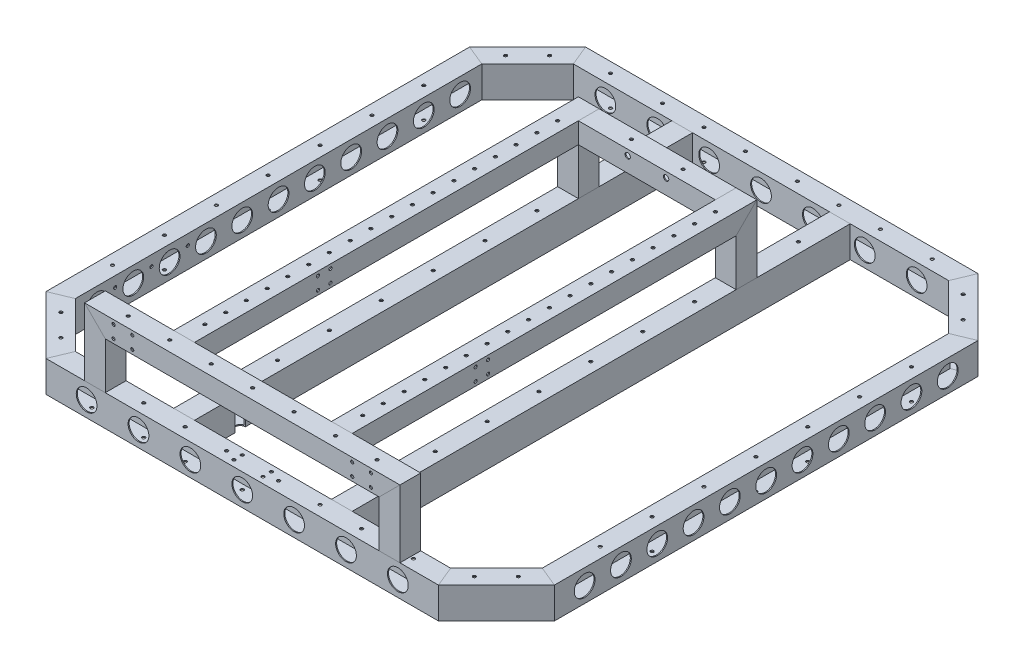
SolidWorks part; units mm, degrees
material "7050-T73510"
ref_plane "前视基准面" through (0, 0, 0) normal (0, 0, 1) x (1, 0, 0)
ref_plane "上视基准面" through (0, 0, 0) normal (0, 1, 0) x (1, 0, 0)
ref_plane "右视基准面" through (0, 0, 0) normal (1, 0, 0) x (0, 0, -1)
sketch "草图1" plane through (0, 0, 0) normal (0, 1, 0) x (1, 0, 0)
  line L0 (-185, 250) -> (-235, 200)
  line L1 (-185, -250) -> (185, -250)
  line L2 (-235, -200) -> (-235, 200)
  line L3 (-185, 250) -> (185, 250)
  line L4 (235, -200) -> (235, 200)
  line L5 (-215, -250) -> (215, 250) construction
  line L6 (-215, 250) -> (215, -250) construction
  line L7 (-235, 0) -> (235, 0) construction
  line L8 (0, 250) -> (0, -250) construction
  line L9 (185, 250) -> (235, 200)
  line L10 (185, -250) -> (235, -200)
  line L11 (-185, -250) -> (-235, -200)
  line L12 (-76, 250) -> (-76, -250)
  line L13 (76, 250) -> (76, -250)
  line L14 (-235, 30) -> (235, 30)
  line L15 (-235, -30) -> (235, -30)
  point P0 (0, 0)
  dimension "D1" = 470
  dimension "D2" = 500
  dimension "D3" = 370
  dimension "D4" = 30
  dimension "D5" = 76
  dimension "D6" = 76
other "Wl 30X20X1(1)"
ref_plane "基准面1" through (-235, 0, 200) normal (0, 0, -1) x (-1, 0, 0)
sketch "草图11" plane through (-235, 0, 200) normal (0, 0, -1) x (-1, 0, 0)
  line L0 (-9, -14) -> (-9, 14)
  line L1 (-10, -15) -> (10, -15)
  line L2 (-10, -15) -> (-10, 15)
  line L3 (-10, 15) -> (10, 15)
  line L4 (10, -15) -> (10, 15)
  line L5 (-10, -15) -> (10, 15) construction
  line L6 (-10, 15) -> (10, -15) construction
  line L7 (-9, 14) -> (9, 14)
  line L8 (9, -14) -> (9, 14)
  line L9 (-9, -14) -> (9, -14)
  point P0 (0, 0)
  point P10 (0, 0)
  dimension "D1" = 20
  dimension "D2" = 30
  dimension "D3" = 1
ref_plane "基准面2" through (76, 0, 0) normal (1, 0, 0) x (0, 0, -1)
ref_plane "基准面3" through (-76, 0, 0) normal (1, 0, 0) x (0, 0, -1)
ref_plane "基准面4" through (0, 0, 250) normal (0, 0, 1) x (1, 0, 0)
sketch "草图14" plane through (0, 0, 250) normal (0, 0, 1) x (1, 0, 0)
  line L0 (0, 0) -> (0, 95) construction
  line L1 (-142, 15) -> (-142, 70)
  line L2 (-189.1421, 15) -> (189.1421, 15) construction
  line L3 (142, 15) -> (142, 70)
  line L4 (-142, 70) -> (142, 70)
  dimension "D1" = 55
  dimension "D2" = 142
other "Wl 20X20X1(1)"
ref_plane "基准面5" through (-142, 15, 250) normal (0, 1, 0) x (-1, 0, 0)
sketch "草图16" plane through (-142, 15, 250) normal (0, 1, 0) x (-1, 0, 0)
  line L8 (-9, -9) -> (9, -9)
  line L9 (-10, -10) -> (10, -10)
  line L10 (-10, -10) -> (-10, 10)
  line L11 (-10, 10) -> (10, 10)
  line L12 (10, -10) -> (10, 10)
  line L13 (9, -9) -> (9, 9)
  line L14 (-9, 9) -> (9, 9)
  line L15 (-9, -9) -> (-9, 9)
  point P4 (0, 0)
  dimension "D1" = 20
  dimension "D2" = 20
sketch "草图12" plane through (76, 0, 0) normal (1, 0, 0) x (0, 0, -1)
  line L0 (-260, 15) -> (-240, 15) construction
  line L2 (260, 15) -> (240, 15) construction
  line L3 (140, 15) -> (140, 70)
  line L4 (140, 70) -> (-240, 70)
  line L5 (204.1421, 15) -> (260, 15) construction
  line L6 (-240, 15) -> (-240, 80) construction
  line L7 (260, -15) -> (260, 15) construction
  dimension "D1" = 55
  dimension "D2" = 120
sketch "草图13" plane through (-76, 0, 0) normal (1, 0, 0) x (0, 0, -1)
  line L1 (140, 70) -> (-240, 70) construction
  line L2 (140, 15) -> (140, 70) construction
  line L4 (140, 70) -> (-240, 70)
  line L5 (140, 15) -> (140, 70)
other "Wl 20X20X1(2)"
ref_plane "基准面6" through (76, 70, -140) normal (0, 0, 1) x (0, -1, 0)
sketch "草图17" plane through (76, 70, -140) normal (0, 0, 1) x (0, -1, 0)
  line L8 (-9, -9) -> (9, -9)
  line L9 (-10, -10) -> (10, -10)
  line L10 (-10, -10) -> (-10, 10)
  line L11 (-10, 10) -> (10, 10)
  line L12 (10, -10) -> (10, 10)
  line L13 (9, -9) -> (9, 9)
  line L14 (-9, 9) -> (9, 9)
  line L15 (-9, -9) -> (-9, 9)
  point P4 (0, 0)
  dimension "D1" = 20
  dimension "D2" = 20
ref_plane "基准面7" through (0, 70, 0) normal (0, 1, 0) x (1, 0, 0)
sketch "草图18" plane through (0, 70, 0) normal (0, 1, 0) x (1, 0, 0)
  line L0 (-66, 140) -> (66, 140)
  line L1 (189.1421, 260) -> (-189.1421, 260) construction
  line L4 (-66, -240) -> (-66, 150) construction
  line L5 (66, -240) -> (66, 150) construction
  dimension "D1" = 120
other "Wl 20X20X1(3)"
ref_plane "基准面8" through (-66, 70, -140) normal (1, 0, 0) x (0, 0, -1)
sketch "草图19" plane through (-66, 70, -140) normal (1, 0, 0) x (0, 0, -1)
  line L8 (-9, -9) -> (9, -9)
  line L9 (-10, -10) -> (10, -10)
  line L10 (-10, -10) -> (-10, 10)
  line L11 (-10, 10) -> (10, 10)
  line L12 (10, -10) -> (10, 10)
  line L13 (9, -9) -> (9, 9)
  line L14 (-9, 9) -> (9, 9)
  line L15 (-9, -9) -> (-9, 9)
  point P4 (0, 0)
  dimension "D1" = 20
  dimension "D2" = 20
sketch "草图20" plane through (0, -15, 0) normal (0, -1, 0) x (1, 0, 0)
  line L0 (0, 260) -> (0, -260) construction
  line L1 (-189.1421, 260) -> (189.1421, 260) construction
  line L2 (189.1421, -260) -> (-189.1421, -260) construction
  line L3 (-66, 240) -> (-66, -240) construction
  line L4 (-180.8579, 240) -> (180.8579, 240) construction
  circle A0 centre (-66, 196) radius 5
  circle A1 centre (66, 196) radius 5
  dimension "D1" = 44
  dimension "D2" = 10
extrude "切除-拉伸1" cut sketch "草图20" against normal blind 30
sketch "草图21" plane through (0, -15, 0) normal (0, -1, 0) x (1, 0, 0)
  line L0 (-185, 250) -> (185, 250) construction
  line L1 (0, -250) -> (0, 250) construction
  line L2 (0, 250) -> (0, 337.4605) construction
  line L3 (-225, 0) -> (224.3825, 0) construction
  line L4 (-225, -195.8579) -> (-225, 195.8579) construction
  line L5 (-235, 0) -> (235, 0) construction
  line L7 (-14, 246) -> (14, 246) construction
  line L8 (-14, 246) -> (-14, 254) construction
  line L9 (-14, 254) -> (14, 254) construction
  line L10 (14, 246) -> (14, 254) construction
  line L11 (-14, 246) -> (14, 254) construction
  line L12 (-14, 254) -> (14, 246) construction
  circle A0 centre (25, 250) radius 1.5
  circle A1 centre (65, 250) radius 1.5
  circle A2 centre (105, 250) radius 1.5
  circle A3 centre (155, 250) radius 1.5
  circle A4 centre (-155, 250) radius 1.5
  circle A5 centre (-105, 250) radius 1.5
  circle A6 centre (-65, 250) radius 1.5
  circle A7 centre (-25, 250) radius 1.5
  circle A8 centre (-25, -250) radius 1.5
  circle A9 centre (-65, -250) radius 1.5
  circle A10 centre (-105, -250) radius 1.5
  circle A11 centre (-155, -250) radius 1.5
  circle A12 centre (155, -250) radius 1.5
  circle A13 centre (105, -250) radius 1.5
  circle A14 centre (65, -250) radius 1.5
  circle A15 centre (25, -250) radius 1.5
  circle A16 centre (-14, 254) radius 1.5
  circle A17 centre (-14, 246) radius 1.5
  circle A18 centre (14, 246) radius 1.5
  circle A19 centre (14, 254) radius 1.5
  dimension "D1" = 3
  dimension "D2" = 25
  dimension "D3" = 3
  dimension "D4" = 40
  dimension "D5" = 3
  dimension "D6" = 40
  dimension "D7" = 3
  dimension "D8" = 50
  dimension "D11" = 3
  dimension "D12" = 3
  dimension "D9" = 28
  dimension "D10" = 8
extrude "切除-拉伸2" cut sketch "草图21" against normal blind 30
sketch "草图22" plane through (0, -15, 0) normal (0, -1, 0) x (1, 0, 0)
  line L0 (-245, 0) -> (245, 0) construction
  line L1 (-245, -204.1421) -> (-245, 204.1421) construction
  line L2 (245, 204.1421) -> (245, -204.1421) construction
  line L3 (0, 260) -> (0, -260) construction
  line L4 (-189.1421, 260) -> (189.1421, 260) construction
  line L5 (189.1421, -260) -> (-189.1421, -260) construction
  line L6 (-235, 200) -> (-235, -200) construction
  line L7 (-76, -250) -> (-76, 250) construction
  line L8 (235, 200) -> (235, -200) construction
  circle A0 centre (-235, 0) radius 1.5
  circle A1 centre (-235, 50) radius 1.5
  circle A2 centre (-235, 100) radius 1.5
  circle A3 centre (-235, 150) radius 1.5
  circle A4 centre (-235, -150) radius 1.5
  circle A5 centre (-235, -100) radius 1.5
  circle A6 centre (-235, -50) radius 1.5
  circle A7 centre (-76, 0) radius 1.5
  circle A8 centre (-76, 50) radius 1.5
  circle A9 centre (-76, 100) radius 1.5
  circle A10 centre (-76, 150) radius 1.5
  circle A11 centre (-76, 200) radius 1.5
  circle A12 centre (-76, -200) radius 1.5
  circle A13 centre (-76, -150) radius 1.5
  circle A14 centre (-76, -100) radius 1.5
  circle A15 centre (-76, -50) radius 1.5
  circle A16 centre (76, -50) radius 1.5
  circle A17 centre (76, -100) radius 1.5
  circle A18 centre (76, -150) radius 1.5
  circle A19 centre (76, -200) radius 1.5
  circle A20 centre (76, 200) radius 1.5
  circle A21 centre (76, 150) radius 1.5
  circle A22 centre (76, 100) radius 1.5
  circle A23 centre (76, 50) radius 1.5
  circle A24 centre (76, 0) radius 1.5
  circle A25 centre (235, -50) radius 1.5
  circle A26 centre (235, -100) radius 1.5
  circle A27 centre (235, -150) radius 1.5
  circle A28 centre (235, 150) radius 1.5
  circle A29 centre (235, 100) radius 1.5
  circle A30 centre (235, 50) radius 1.5
  circle A31 centre (235, 0) radius 1.5
  dimension "D1" = 3
  dimension "D3" = 3
  dimension "D2" = 4
  dimension "D4" = 5
extrude "切除-拉伸3" cut sketch "草图22" against normal blind 30
sketch "草图23" plane through (0, 80, 0) normal (0, 1, 0) x (1, 0, 0)
  line L0 (0, -260) -> (0, 150) construction
  line L1 (152, -260) -> (-152, -260) construction
  line L2 (66, 150) -> (-66, 150) construction
  line L3 (-76, 150) -> (-76, -260) construction
  line L4 (-66, 150) -> (-86, 150) construction
  line L5 (-86, 150) -> (-66, 150) construction
  circle A0 centre (-76, 120) radius 1.5
  circle A1 centre (-76, 100) radius 1.5
  circle A2 centre (-76, 80) radius 1.5
  circle A3 centre (-76, 60) radius 1.5
  circle A4 centre (-76, 40) radius 1.5
  circle A5 centre (-76, 20) radius 1.5
  circle A6 centre (-76, 0) radius 1.5
  circle A7 centre (-76, -20) radius 1.5
  circle A8 centre (-76, -40) radius 1.5
  circle A9 centre (-76, -60) radius 1.5
  circle A10 centre (-76, -80) radius 1.5
  circle A11 centre (-76, -100) radius 1.5
  circle A12 centre (-76, -120) radius 1.5
  circle A13 centre (-76, -140) radius 1.5
  circle A14 centre (-76, -160) radius 1.5
  circle A15 centre (-76, -180) radius 1.5
  circle A16 centre (-76, -200) radius 1.5
  circle A17 centre (-76, -220) radius 1.5
  circle A18 centre (76, -220) radius 1.5
  circle A19 centre (76, -200) radius 1.5
  circle A20 centre (76, -180) radius 1.5
  circle A21 centre (76, -160) radius 1.5
  circle A22 centre (76, -140) radius 1.5
  circle A23 centre (76, -120) radius 1.5
  circle A24 centre (76, -100) radius 1.5
  circle A25 centre (76, -80) radius 1.5
  circle A26 centre (76, -60) radius 1.5
  circle A27 centre (76, -40) radius 1.5
  circle A28 centre (76, -20) radius 1.5
  circle A29 centre (76, 0) radius 1.5
  circle A30 centre (76, 20) radius 1.5
  circle A31 centre (76, 40) radius 1.5
  circle A32 centre (76, 60) radius 1.5
  circle A33 centre (76, 80) radius 1.5
  circle A34 centre (76, 100) radius 1.5
  circle A35 centre (76, 120) radius 1.5
  dimension "D1" = 3
  dimension "D2" = 30
  dimension "D3" = 18
extrude "切除-拉伸4" cut sketch "草图23" against normal blind 20
extrude "切除-拉伸5" cut sketch "草图24" against normal blind 30
sketch "草图24" plane through (69.8587, -15, 0) normal (0, -1, 0) x (1, 0, 0)
  circle A8 centre (-290.3942, -214.3223) radius 1.5
  circle A9 centre (-269.181, -235.5355) radius 1.5
  circle A10 centre (129.4636, -235.5355) radius 1.5
  circle A11 centre (150.6768, -214.3223) radius 1.5
  circle A12 centre (150.6768, 214.3223) radius 1.5
  circle A13 centre (129.4636, 235.5355) radius 1.5
  circle A14 centre (-290.3942, 214.3223) radius 1.5
  circle A15 centre (-269.181, 235.5355) radius 1.5
extrude "切除-拉伸6" cut sketch "草图25" against normal blind 20
sketch "草图25" plane through (69.8587, 41.0677, 260) normal (0, 0, 1) x (1, 0, 0)
  circle A8 centre (-175.8587, 22.9323) radius 1.5
  circle A9 centre (-175.8587, 34.9323) radius 1.5
  circle A10 centre (-193.8587, 22.9323) radius 1.5
  circle A11 centre (-193.8587, 34.9323) radius 1.5
  circle A12 centre (54.1413, 34.9323) radius 1.5
  circle A13 centre (54.1413, 22.9323) radius 1.5
  circle A14 centre (36.1413, 22.9323) radius 1.5
  circle A15 centre (36.1413, 34.9323) radius 1.5
sketch "草图26" plane through (0, 80, 0) normal (0, 1, 0) x (1, 0, 0)
  line L0 (-152, -250) -> (152, -250) construction
  line L1 (-152, -240) -> (-152, -260) construction
  line L2 (152, -240) -> (152, -260) construction
  line L3 (0, -260) -> (0, -240) construction
  line L4 (152, -260) -> (-152, -260) construction
  line L5 (152, -240) -> (-152, -240) construction
  line L6 (0, 130) -> (0, 150) construction
  line L7 (66, 130) -> (-66, 130) construction
  line L8 (66, 150) -> (-66, 150) construction
  circle A0 centre (0, -250) radius 1.5
  circle A1 centre (40, -250) radius 1.5
  circle A2 centre (80, -250) radius 1.5
  circle A3 centre (120, -250) radius 1.5
  circle A4 centre (-120, -250) radius 1.5
  circle A5 centre (-80, -250) radius 1.5
  circle A6 centre (-40, -250) radius 1.5
  circle A7 centre (-25, 140) radius 1.5
  circle A8 centre (25, 140) radius 1.5
  dimension "D1" = 3
  dimension "D3" = 3
  dimension "D4" = 25
  dimension "D2" = 4
extrude "切除-拉伸7" cut sketch "草图26" against normal blind 20
extrude "切除-拉伸8" cut sketch "草图27" against normal blind 20
sketch "草图27" plane through (69.8587, 41.0677, -130) normal (0, 0, 1) x (1, 0, 0)
  circle A2 centre (-51.3587, 33.4323) radius 2.6
  circle A3 centre (-88.3587, 33.4323) radius 2.6
extrude "切除-拉伸9" cut sketch "草图28" against normal through all
sketch "草图28" plane through (-86, 41.0677, 0) normal (-1, 0, 0) x (0, 0, 1)
  circle A4 centre (109, 22.9323) radius 1.5
  circle A5 centre (121, 22.9323) radius 1.5
  circle A6 centre (109, 34.9323) radius 1.5
  circle A7 centre (121, 34.9323) radius 1.5
sketch "草图29" plane through (0, 80, 0) normal (0, 1, 0) x (1, 0, 0)
  line L0 (86, -240) -> (86, 150) construction
  line L1 (66, 150) -> (-66, 150) construction
  line L2 (-86, -240) -> (-86, 150) construction
  line L3 (86, 150) -> (66, 150) construction
  line L4 (-66, 150) -> (-86, 150) construction
  line L5 (152, -260) -> (152, -240) construction
  line L6 (152, -240) -> (-152, -240) construction
  line L7 (-152, -260) -> (-152, -240) construction
  line L8 (152, -260) -> (-152, -260) construction
  line L9 (86, -240) -> (86, 150)
  line L10 (66, 150) -> (-66, 150)
  line L11 (-86, -240) -> (-86, 150)
  line L12 (86, 150) -> (66, 150)
  line L13 (-66, 150) -> (-86, 150)
  line L14 (152, -260) -> (152, -240)
  line L15 (152, -240) -> (-152, -240)
  line L16 (-152, -260) -> (-152, -240)
  line L17 (152, -260) -> (-152, -260)
  circle A0 centre (76, -60) radius 1.5 construction
  circle A1 centre (76, -100) radius 1.5 construction
  circle A2 centre (76, -140) radius 1.5 construction
  circle A3 centre (76, -180) radius 1.5 construction
  circle A4 centre (-76, -180) radius 1.5 construction
  circle A5 centre (-76, -140) radius 1.5 construction
  circle A6 centre (-76, -100) radius 1.5 construction
  circle A7 centre (-76, -60) radius 1.5 construction
  circle A8 centre (-76, -20) radius 1.5 construction
  circle A9 centre (76, -20) radius 1.5 construction
  circle A10 centre (76, 20) radius 1.5 construction
  circle A11 centre (-76, 20) radius 1.5 construction
  circle A12 centre (76, 60) radius 1.5 construction
  circle A13 centre (-25, 140) radius 1.5 construction
  circle A14 centre (25, 140) radius 1.5 construction
  circle A15 centre (76, 100) radius 1.5 construction
  circle A16 centre (-76, 60) radius 1.5 construction
  circle A17 centre (-76, 100) radius 1.5 construction
  circle A18 centre (76, -60) radius 1.5
  circle A19 centre (76, -100) radius 1.5
  circle A20 centre (76, -140) radius 1.5
  circle A21 centre (76, -180) radius 1.5
  circle A22 centre (-76, -180) radius 1.5
  circle A23 centre (-76, -140) radius 1.5
  circle A24 centre (-76, -100) radius 1.5
  circle A25 centre (-76, -60) radius 1.5
  circle A26 centre (-76, -20) radius 1.5
  circle A27 centre (76, -20) radius 1.5
  circle A28 centre (76, 20) radius 1.5
  circle A29 centre (-76, 20) radius 1.5
  circle A30 centre (76, 60) radius 1.5
  circle A31 centre (-25, 140) radius 1.5
  circle A32 centre (25, 140) radius 1.5
  circle A33 centre (76, 100) radius 1.5
  circle A34 centre (-76, 60) radius 1.5
  circle A35 centre (-76, 100) radius 1.5
  circle A36 centre (120, -250) radius 1.5 construction
  circle A37 centre (80, -250) radius 1.5 construction
  circle A38 centre (40, -250) radius 1.5 construction
  circle A39 centre (0, -250) radius 1.5 construction
  circle A40 centre (-40, -250) radius 1.5 construction
  circle A41 centre (-80, -250) radius 1.5 construction
  circle A42 centre (-120, -250) radius 1.5 construction
  circle A43 centre (120, -250) radius 1.5
  circle A44 centre (80, -250) radius 1.5
  circle A45 centre (40, -250) radius 1.5
  circle A46 centre (0, -250) radius 1.5
  circle A47 centre (-40, -250) radius 1.5
  circle A48 centre (-80, -250) radius 1.5
  circle A49 centre (-120, -250) radius 1.5
sketch "草图30" plane through (-245, 0, 0) normal (-1, 0, 0) x (0, 0, 1)
  line L0 (-204.1421, 0) -> (204.1421, 0) construction
  line L1 (-204.1421, 15) -> (-204.1421, -15) construction
  line L2 (204.1421, -15) -> (204.1421, 15) construction
  line L4 (0, 15) -> (0, -15) construction
  line L5 (-204.1421, 15) -> (204.1421, 15) construction
  line L6 (-204.1421, -15) -> (204.1421, -15) construction
  circle A0 centre (0, 0) radius 10
  circle A1 centre (35, 0) radius 10
  circle A2 centre (70, 0) radius 10
  circle A3 centre (105, 0) radius 10
  circle A4 centre (140, 0) radius 10
  circle A5 centre (175, 0) radius 10
  circle A6 centre (-175, 0) radius 10
  circle A7 centre (-140, 0) radius 10
  circle A8 centre (-105, 0) radius 10
  circle A9 centre (-70, 0) radius 10
  circle A10 centre (-35, 0) radius 10
  dimension "D1" = 20
  dimension "D2" = 6
extrude "切除-拉伸10" cut sketch "草图30" against normal blind 20
ref_plane "基准面9" through (0, 0, 0) normal (-1, 0, 0) x (0, 0, 1)
sketch "草图31" plane through (245, 0, 0) normal (1, 0, 0) x (0, 0, -1)
  line L0 (-204.1421, 0) -> (204.1421, 0) construction
  line L1 (-204.1421, 15) -> (-204.1421, -15) construction
  line L2 (204.1421, -15) -> (204.1421, 15) construction
  line L3 (0, -15) -> (0, 15) construction
  line L4 (-204.1421, -15) -> (204.1421, -15) construction
  line L5 (-204.1421, 15) -> (204.1421, 15) construction
  circle A0 centre (0, 0) radius 10
  circle A1 centre (35, 0) radius 10
  circle A2 centre (70, 0) radius 10
  circle A3 centre (105, 0) radius 10
  circle A4 centre (140, 0) radius 10
  circle A5 centre (175, 0) radius 10
  circle A6 centre (-175, 0) radius 10
  circle A7 centre (-140, 0) radius 10
  circle A8 centre (-105, 0) radius 10
  circle A9 centre (-70, 0) radius 10
  circle A10 centre (-35, 0) radius 10
  dimension "D1" = 20
  dimension "D2" = 6
extrude "切除-拉伸11" cut sketch "草图31" against normal blind 20
sketch "草图32" plane through (0, 0, -260) normal (0, 0, -1) x (-1, 0, 0)
  line L0 (0, -15) -> (0, 15) construction
  line L1 (-189.1421, -15) -> (189.1421, -15) construction
  line L2 (-189.1421, 15) -> (189.1421, 15) construction
  line L3 (-189.1421, 0) -> (189.1421, 0) construction
  line L4 (-189.1421, 15) -> (-189.1421, -15) construction
  line L5 (189.1421, -15) -> (189.1421, 15) construction
  circle A0 centre (0, 0) radius 10
  circle A1 centre (50, 0) radius 10
  circle A2 centre (100, 0) radius 10
  circle A3 centre (150, 0) radius 10
  circle A4 centre (-150, 0) radius 10
  circle A5 centre (-100, 0) radius 10
  circle A6 centre (-50, 0) radius 10
  dimension "D1" = 20
  dimension "D2" = 4
extrude "切除-拉伸13" cut sketch "草图32" against normal blind 20
sketch "草图33" plane through (0, 0, 260) normal (0, 0, 1) x (1, 0, 0)
  line L0 (0, 15) -> (0, -15) construction
  line L1 (-189.1421, 15) -> (189.1421, 15) construction
  line L2 (-189.1421, -15) -> (189.1421, -15) construction
  line L3 (-189.1421, 0) -> (189.1421, 0) construction
  line L4 (-189.1421, 15) -> (-189.1421, -15) construction
  line L5 (189.1421, -15) -> (189.1421, 15) construction
  circle A0 centre (0, 0) radius 10
  circle A1 centre (50, 0) radius 10
  circle A2 centre (100, 0) radius 10
  circle A3 centre (150, 0) radius 10
  circle A4 centre (-150, 0) radius 10
  circle A5 centre (-100, 0) radius 10
  circle A6 centre (-50, 0) radius 10
  dimension "D1" = 20
  dimension "D2" = 4
extrude "切除-拉伸14" cut sketch "草图33" against normal blind 20
sketch "草图34" plane through (-245, 0, 0) normal (-1, 0, 0) x (0, 0, 1)
  line L0 (150, 0) -> (165, 0) construction
  line L1 (157.5, 0) -> (157.5, 15) construction
  line L2 (-204.1421, 15) -> (204.1421, 15) construction
  circle A0 centre (140, 0) radius 10 construction
  circle A1 centre (175, 0) radius 10 construction
  circle A2 centre (157.5, 5) radius 1.5
  circle A3 centre (122.5, 5) radius 1.5
  circle A4 centre (87.5, 5) radius 1.5
  point P13 (0, 0)
  dimension "D1" = 3
  dimension "D2" = 10
  dimension "D3" = 3
extrude "切除-拉伸15" cut sketch "草图34" against normal blind 20
